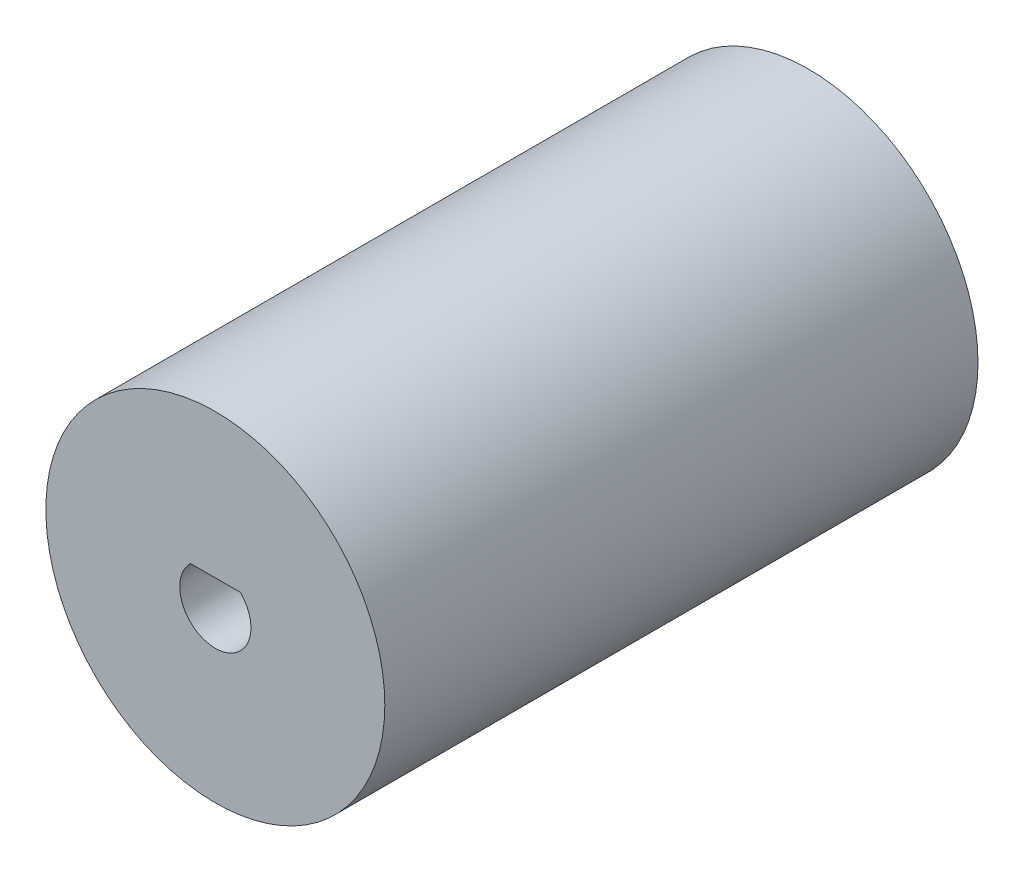
SolidWorks part; units mm, degrees
material "Plastique personnalisé"
ref_plane "Plan de face" through (0, 0, 0) normal (0, 0, 1) x (1, 0, 0)
ref_plane "Plan de dessus" through (0, 0, 0) normal (0, 1, 0) x (1, 0, 0)
ref_plane "Plan de droite" through (0, 0, 0) normal (1, 0, 0) x (0, 0, -1)
sketch "Esquisse1" plane through (0, 0, 0) normal (0, 0, 1) x (1, 0, 0)
  circle A0 centre (0, 0) radius 10
  circle A1 centre (0, 0) radius 6.05
  dimension "D1" = 20
  dimension "D2" = 12.1
extrude "Boss.-Extru.1" add sketch "Esquisse1" along normal blind 35 contours A0 A1 | A1 region at (-9.7172, 0, 0) region at (0, 0, 0)
extrude "Enlèv. mat.-Extru.1" cut sketch "Esquisse1<3>" along normal blind 25 contours A1 region at (0, 0, 0)
sketch "Esquisse1<3>" plane through (0, 0, 0) normal (0, 0, 1) x (1, 0, 0) same geometry as "Esquisse1"
sketch "Esquisse2" plane through (0, 0, 35) normal (0, 0, 1) x (1, 0, 0)
  line L0 (-1.4697, 1.5) -> (1.4697, 1.5)
  arc A0 (-1.4697, 1.5) -> (1.4697, 1.5) centre (0, 0) ccw
  dimension "D1" = 1.5
  dimension "D2" = 2.1
extrude "Enlèv. mat.-Extru.2" cut sketch "Esquisse2" against normal blind 9
